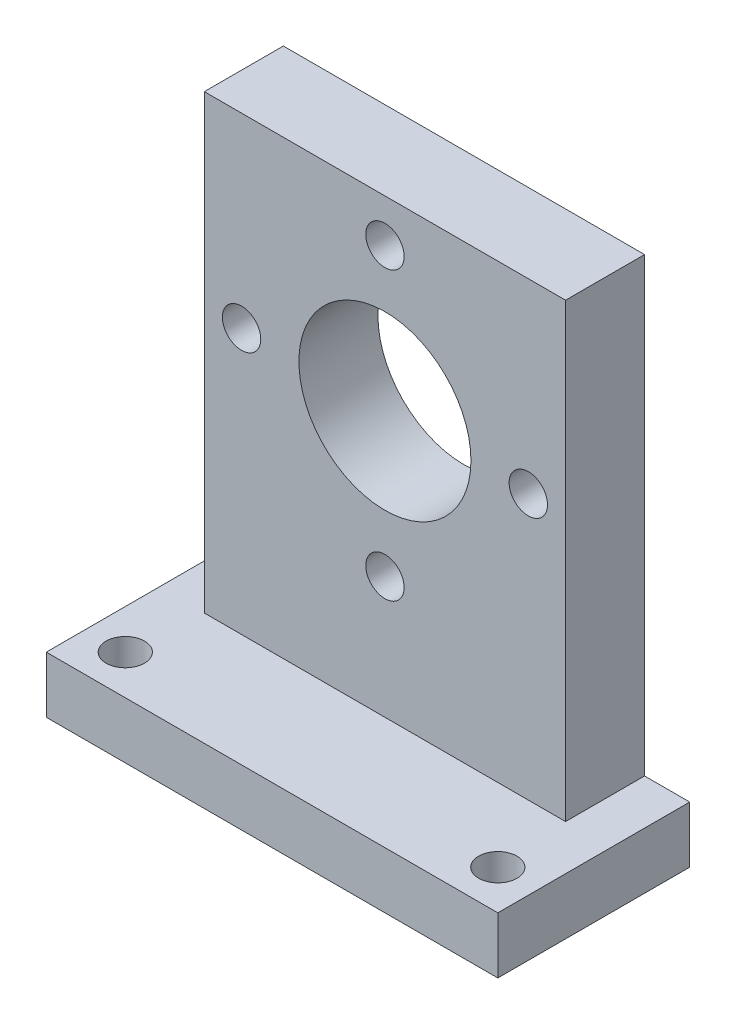
SolidWorks part; units mm, degrees
ref_plane "Front Plane" through (0, 0, 0) normal (0, 0, 1) x (1, 0, 0)
ref_plane "Top Plane" through (0, 0, 0) normal (0, 1, 0) x (1, 0, 0)
ref_plane "Right Plane" through (0, 0, 0) normal (1, 0, 0) x (0, 0, -1)
sketch "Sketch1" plane through (0, 0, 0) normal (0, 1, 0) x (1, 0, 0)
  line L1 (-20, 13.5) -> (20, 13.5)
  line L2 (-20, 13.5) -> (-20, -13.5)
  line L3 (-20, -13.5) -> (20, -13.5)
  line L4 (20, 13.5) -> (20, -13.5)
  line L5 (-20, 13.5) -> (20, -13.5) construction
  line L6 (-20, -13.5) -> (20, 13.5) construction
  line L7 (-16, 3.5) -> (16, 3.5)
  line L8 (-16, 3.5) -> (-16, -3.5)
  line L9 (-16, -3.5) -> (16, -3.5)
  line L10 (16, 3.5) -> (16, -3.5)
  line L11 (-16, 3.5) -> (16, -3.5) construction
  line L12 (-16, -3.5) -> (16, 3.5) construction
  point P0 (0, 0)
  point P6 (0, 0)
  dimension "D1" = 40
  dimension "D2" = 27
  dimension "D3" = 7
  dimension "D4" = 32
extrude "Boss-Extrude1" add sketch "Sketch1" along normal blind 5 contours L10 L7 L8 L9 | L2 L1 L4 L3 region at (0, 0, 0)
extrude "Boss-Extrude2" add sketch "Sketch1<3>" along normal blind 45 contours L10 L7 L8 L9 region at (0, 0, 0)
sketch "Sketch1<3>" plane through (0, 0, 0) normal (0, 1, 0) x (1, 0, 0) same geometry as "Sketch1"
sketch "Sketch2" plane through (0, 0, 3.5) normal (0, 0, 1) x (1, 0, 0)
  line L0 (-20, 5) -> (20, 5) construction
  circle A0 centre (0, 28.5) radius 7.62
  dimension "D1" = 15.24
  dimension "D2" = 23.5
extrude "Cut-Extrude1" cut sketch "Sketch2" against normal up to next
sketch "Sketch4" plane through (0, 0, 3.5) normal (0, 0, 1) x (1, 0, 0)
  line L0 (0, 45) -> (0, 28.5) construction
  line L1 (-16, 45) -> (16, 45) construction
  circle A0 centre (0, 41.2) radius 1.7
  circle A1 centre (0, 28.5) radius 7.62 construction
  circle A2 centre (12.7, 28.5) radius 1.7
  circle A3 centre (0, 15.8) radius 1.7
  circle A4 centre (-12.7, 28.5) radius 1.7
  point P18 (0, 28.5)
  dimension "D2" = 3.4
  dimension "D1" = 12.7
  dimension "D3" = 4
extrude "Cut-Extrude2" cut sketch "Sketch4" against normal up to next
sketch "Sketch5" plane through (0, 5, 0) normal (0, 1, 0) x (1, 0, 0)
  line L1 (-20, 13.5) -> (20, 13.5) construction
  line L2 (-20, 13.5) -> (-20, -13.5) construction
  line L3 (-20, -13.5) -> (20, -13.5) construction
  line L4 (0, 13.5) -> (0, -13.5) construction
  circle A0 centre (-16.5, 10) radius 1.7
  circle A2 centre (-16.5, -10) radius 1.7
  circle A4 centre (16.5, -10) radius 1.7
  circle A5 centre (16.5, 10) radius 1.7
  dimension "D3" = 3.4
  dimension "D1" = 3.5
  dimension "D2" = 3.5
  dimension "D4" = 3.5
extrude "Cut-Extrude3" cut sketch "Sketch5" against normal up to next
sketch "Sketch7" plane through (0, 5, 0) normal (0, 1, 0) x (1, 0, 0)
  line L0 (-20, 13.5) -> (-20, -13.5) construction
  line L1 (-20, 3.5) -> (20, 3.5)
  line L2 (-20, 3.5) -> (-20, 13.5)
  line L3 (-20, 13.5) -> (20, 13.5)
  line L4 (20, 3.5) -> (20, 13.5)
  line L5 (-16, 3.5) -> (16, 3.5) construction
extrude "Cut-Extrude5" cut sketch "Sketch7" against normal up to next
sketch "Sketch8" plane through (0, 0, -3.5) normal (0, 0, -1) x (-1, 0, 0)
  line L0 (-12.7, 28.5) -> (-12.7, 2.5) construction
  line L1 (0, 0) -> (0, 13.0763) construction
  line L5 (-20, 5) -> (-20, 0) construction
  circle A0 centre (-12.7, 2.5) radius 1.7
  circle A1 centre (12.7, 2.5) radius 1.7
  circle A2 centre (-12.7, 28.5) radius 1.7 construction
  point P9 (-20, 2.5)
extrude "Cut-Extrude6" cut sketch "Sketch8" against normal blind 6.35
